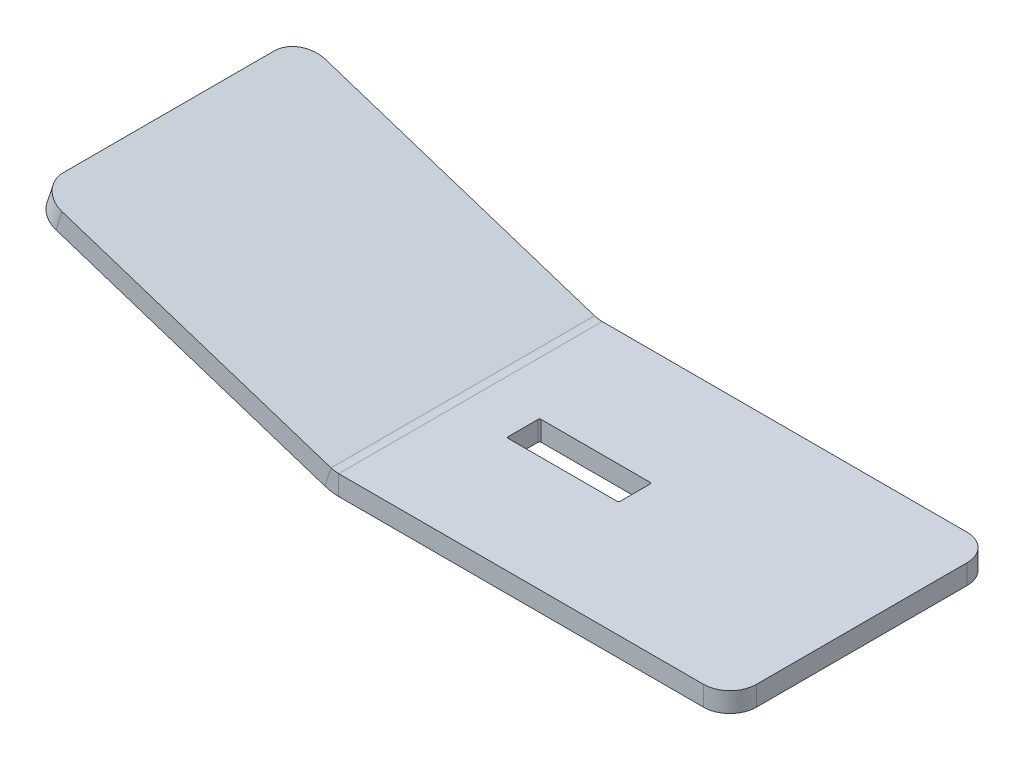
SolidWorks part; units mm, degrees
note: The reader was unsure of these and kept them because the rebuilt part matched: flange length of "Edge-Flange1".
material "PL,A36"
ref_plane "Front" through (0, 0, 0) normal (0, 0, 1) x (1, 0, 0)
ref_plane "Top" through (0, 0, 0) normal (0, 1, 0) x (1, 0, 0)
ref_plane "Right" through (0, 0, 0) normal (1, 0, 0) x (0, 0, -1)
sketch "Sketch2" plane through (0, 0, 0) normal (0, 1, 0) x (1, 0, 0)
  line L1 (0, 0) -> (95.25, 0)
  line L2 (0, 0) -> (0, 63.5)
  line L3 (0, 63.5) -> (95.25, 63.5)
  line L4 (95.25, 0) -> (95.25, 63.5)
  dimension "D1" = 63.5
  dimension "D2" = 95.25
base flange "Base-Flange1" sketch "Sketch2" thickness 4.7752 reverse thickness direction no parameters "D1"=5.9436
edge flange "Edge-Flange1" sketch "Sketch9" flange angle 162 flange length 76.2 flange position material outside bend radius 5.9436 thickness 4.7752 relief rectangular parameters "D1"=7.9502, "D6"=10
sketch "Sketch9" plane through (0, 0, 0) normal (-0.309, -0.9511, 0) x (0, 0, 1)
  line L2 (-63.5, 0) -> (-63.5, 75.4437)
  line L3 (-63.5, 75.4437) -> (0, 75.4437)
  line L4 (0, 75.4437) -> (0, 0)
  line L7 (-63.5, 0) -> (0, 0) construction
  line L8 (-63.5, 0) -> (0, 0)
bend "EdgeBend1" bend radius 5.9436 bend angle 18 parameters "D5"=1
fillet "Fillet1" radius 6.35 4 edges at (95.25, -2.3876, -63.5) (95.25, -2.3876, 0) (-72.489, 21.0426, -63.5) (-72.489, 21.0426, 0)
sketch "Sketch10" plane through (0, 0, 0) normal (0, 1, 0) x (1, 0, 0)
  line L0 (0.9414, 0) -> (0.9414, 63.5) construction
  line L1 (13.6414, 35.7188) -> (40.6289, 35.7187)
  line L2 (13.6414, 35.7188) -> (13.6414, 27.7812)
  line L3 (13.6414, 27.7812) -> (40.6289, 27.7813)
  line L4 (40.6289, 35.7187) -> (40.6289, 27.7813)
  line L5 (95.25, 6.35) -> (95.25, 57.15) construction
  point P6 (40.6289, 31.75)
  point P9 (95.25, 31.75)
  dimension "D1" = 7.9375
  dimension "D2" = 26.9875
  dimension "D3" = 12.7
extrude "Cut-Extrude1" cut sketch "Sketch10" against normal through all normal cut yes
fillet "Fillet2" radius 0.3969 4 edges at (40.6289, -2.3876, -35.7187) (13.6414, -2.3876, -35.7188) (13.6414, -2.3876, -27.7812) (40.6289, -2.3876, -27.7813)
sketch "Bend-Lines1" [suppressed] plane through (0, 0, 0) normal (0, 1, 0) x (1, 0, 0)
sketch "Bounding-Box1" [suppressed] plane through (0, 0, 0) normal (0, 1, 0) x (1, 0, 0)
sheet metal parameters "Sheet-Metal28" thickness 4.7752 parameters "D1"=7.9502
flat pattern "Flat-Pattern28" [suppressed]
sketch "Bend-Lines2" plane through (0, 0, 0) normal (0, 1, 0) x (1, 0, 0)
sketch3d "Bounding-Box2" [suppressed]
  line L0 (-88.9, 38.1, 0) -> (0, 38.1, 0) construction
  line L1 (-88.9, 0, 0) -> (0, 0, 0) construction
  line L2 (-88.9, 38.1, 0) -> (-88.9, 0, 0) construction
  line L3 (0, 38.1, 0) -> (0, 0, 0) construction
sheet metal parameters "Sheet-Metal29" thickness 4.7752 parameters "D1"=7.9502
flat pattern "Flat-Pattern28"
sketch "Bend-Lines2" plane through (0, 0, 0) normal (0, 1, 0) x (1, 0, 0)
  line L0 (-0.3673, 38.1) -> (-0.3673, 0) construction
  line L1 (-0.3673, 38.1) -> (-0.3673, 0) construction
sketch3d "Bounding-Box2" [suppressed]
  line L0 (-76.1783, 38.1, 0) -> (88.9, 38.1, 0) construction
  line L1 (-76.1783, 0, 0) -> (88.9, 0, 0) construction
  line L2 (-76.1783, 38.1, 0) -> (-76.1783, 0, 0) construction
  line L3 (88.9, 38.1, 0) -> (88.9, 0, 0) construction
bend of the flat pattern "Flatten-<EdgeBend1>1"
sheet metal parameters "Sheet-Metal30" thickness 4.7752 parameters "D1"=7.9502
flat pattern "Flat-Pattern28"
sketch "Bend-Lines2" plane through (0, 0, 0) normal (0, 1, 0) x (1, 0, 0)
  line L0 (-0.3673, 63.5) -> (-0.3673, 0) construction
  line L1 (-0.3673, 63.5) -> (-0.3673, 0) construction
sketch3d "Bounding-Box2" [suppressed]
  line L0 (-76.1783, 63.5, 0) -> (95.25, 63.5, 0) construction
  line L1 (-76.1782, 0, 0) -> (95.25, 0, 0) construction
  line L2 (-76.1783, 63.5, 0) -> (-76.1782, 0, 0) construction
  line L3 (95.25, 63.5, 0) -> (95.25, 0, 0) construction
bend of the flat pattern "Flatten-<EdgeBend1>1"
equation "\"Total Cutting Length\"= \"Cutting Length-Outer\" + \"Cutting Length-Inner\""
equation "\"Amount in ft^2\"= \"Bounding Box Area-Blank\" / 144"
